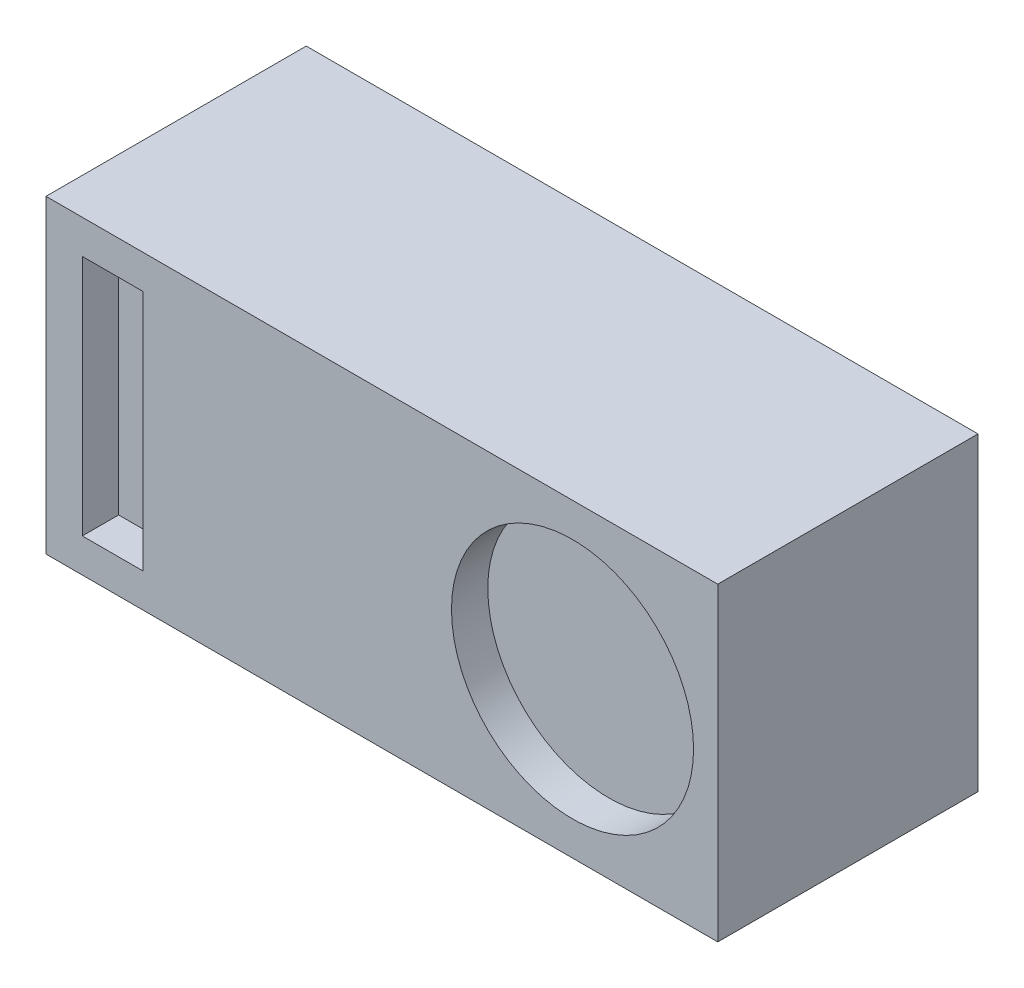
SolidWorks part; units mm, degrees
ref_plane "Front Plane" through (0, 0, 0) normal (0, 0, 1) x (1, 0, 0)
ref_plane "Top Plane" through (0, 0, 0) normal (0, 1, 0) x (1, 0, 0)
ref_plane "Right Plane" through (0, 0, 0) normal (1, 0, 0) x (0, 0, -1)
sketch "Sketch1" plane through (0, 0, 0) normal (0, 0, 1) x (1, 0, 0)
  line L1 (27.75, 12.8) -> (-27.75, 12.8)
  line L2 (27.75, 12.8) -> (27.75, -12.8)
  line L3 (27.75, -12.8) -> (-27.75, -12.8)
  line L4 (-27.75, 12.8) -> (-27.75, -12.8)
  line L5 (0, -12.8) -> (0, 12.8) construction
  line L6 (27.75, 0) -> (-27.75, 0) construction
  line L7 (-19.75, 10) -> (-24.75, 10)
  line L8 (-19.75, 10) -> (-19.75, -10)
  line L9 (-19.75, -10) -> (-24.75, -10)
  line L10 (-24.75, 10) -> (-24.75, -10)
  line L11 (-22.25, -10) -> (-22.25, 10) construction
  line L12 (-19.75, 0) -> (-24.75, 0) construction
  circle A0 centre (15.75, 0) radius 10
  point P0 (0, 0)
  point P4 (-22.25, 0)
  dimension "D3" = 20
  dimension "D7" = 12
  dimension "D1" = 55.5
  dimension "D2" = 25.6
  dimension "D4" = 20
  dimension "D5" = 5
  dimension "D6" = 3
extrude "Boss-Extrude1" add sketch "Sketch1" along normal blind 21.5
extrude "Boss-Extrude2" add sketch "Sketch1<2>" along normal offset from surface (18.5 mm away) 3 contours L7 L10 L9 L8 | A0 region at (-22.25, 0, 0) region at (15.75, 0, 0) up to face at (0, 0, 21.5)
sketch "Sketch1<2>" plane through (0, 0, 0) normal (0, 0, 1) x (1, 0, 0) same geometry as "Sketch1"
